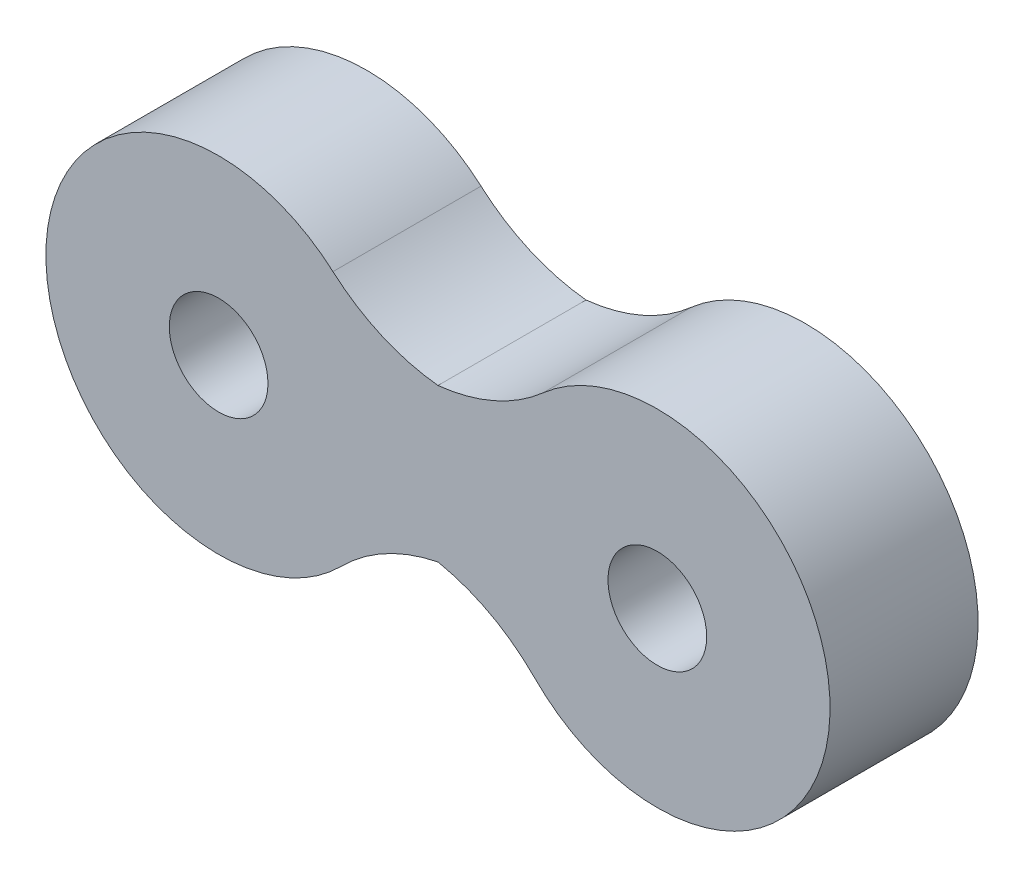
SolidWorks part; units mm, degrees
material "Acrylic (Medium-high impact)"
ref_plane "Front Plane" through (0, 0, 0) normal (0, 0, 1) x (1, 0, 0)
ref_plane "Top Plane" through (0, 0, 0) normal (0, 1, 0) x (1, 0, 0)
ref_plane "Right Plane" through (0, 0, 0) normal (1, 0, 0) x (0, 0, -1)
sketch "스케치1" plane through (0, 0, 0) normal (0, 0, 1) x (1, 0, 0)
  line L0 (1.3601, -0.0164) -> (0.9492, -1.498) construction
  line L1 (0.9492, -1.498) -> (1.2129, -3.0128) construction
  line L2 (0.7762, -10.047) -> (0, -9.9598) construction
  line L3 (0, -9.9598) -> (-0.7762, -10.047) construction
  line L4 (0, -9.9598) -> (0, 0) construction
  line L5 (1.3601, -0.0164) -> (-1.3601, -0.0164) construction
  line L6 (1.3601, -0.0164) -> (1.2129, -3.0128) construction
  line L7 (1.3601, -0.0164) -> (-55.721, 2.7882) construction
  line L8 (1.2129, -3.0128) -> (-55.8682, -0.2082) construction
  line L9 (-55.721, 2.7882) -> (-55.8682, -0.2082) construction
  line L10 (-9.4989, -2.4865) -> (-55.8682, -0.2082) construction
  arc A0 (-1.3601, -0.0164) -> (1.3601, -0.0164) centre (0, -56.4778) cw construction
  arc A1 (-1.2129, -3.0128) -> (1.2129, -3.0128) centre (0, -56.4778) cw construction
  circle A2 centre (-4.445, -1.6698) radius 3.5 construction
  circle A3 centre (4.445, -1.6698) radius 3.5 construction
  arc A4 (-4.445, -1.6698) -> (4.445, -1.6698) centre (0, -56.4778) cw construction
  circle A5 centre (-4.445, -1.6698) radius 1
  circle A6 centre (4.445, -1.6698) radius 1
  circle A7 centre (0, -13.4598) radius 3.5 construction
  circle A8 centre (0, -13.4598) radius 1
  arc A9 (0.7762, -10.047) -> (1.6764, -3.0253) centre (1.5649, -6.5795) cw construction
  arc A10 (-1.6764, -3.0253) -> (-0.7762, -10.047) centre (-1.5649, -6.5795) cw construction
  arc A13 (1.3601, -0.0164) -> (1.2129, -3.0128) centre (4.445, -1.6698) cw
  arc A14 (0.7762, -10.047) -> (-0.7762, -10.047) centre (0, -13.4598) cw construction
  arc A15 (-1.2129, -3.0128) -> (-1.3601, -0.0164) centre (-4.445, -1.6698) cw
  arc A16 (-7.3015, -3.6923) -> (-9.4989, -2.4865) centre (-9.6394, -5.3478) ccw construction
  arc A17 (-1.3601, -0.0164) -> (1.3601, -0.0164) centre (0, -56.4778) cw
  arc A19 (-1.2129, -3.0128) -> (1.2129, -3.0128) centre (0, -56.4778) cw
  dimension "D1" = 2.5
  dimension "D2" = 2
  dimension "D4" = 3.556
  dimension "D7" = 57.15
  dimension "D5" = 8.89
  dimension "D6" = 3
extrude "보스-돌출1" add sketch "스케치1" along normal blind 3 contours A16 A15 A10 A14 A9 A13 L7 L9 L10 A8 A6 A5 region at (0, -1.6532, 0)
fillet "필렛1" radius 3.81 4 edges at (1.2129, -3.0128, 1.5) (-1.2129, -3.0128, 1.5) (1.3601, -0.0164, 1.5) (-1.3601, -0.0164, 1.5)
